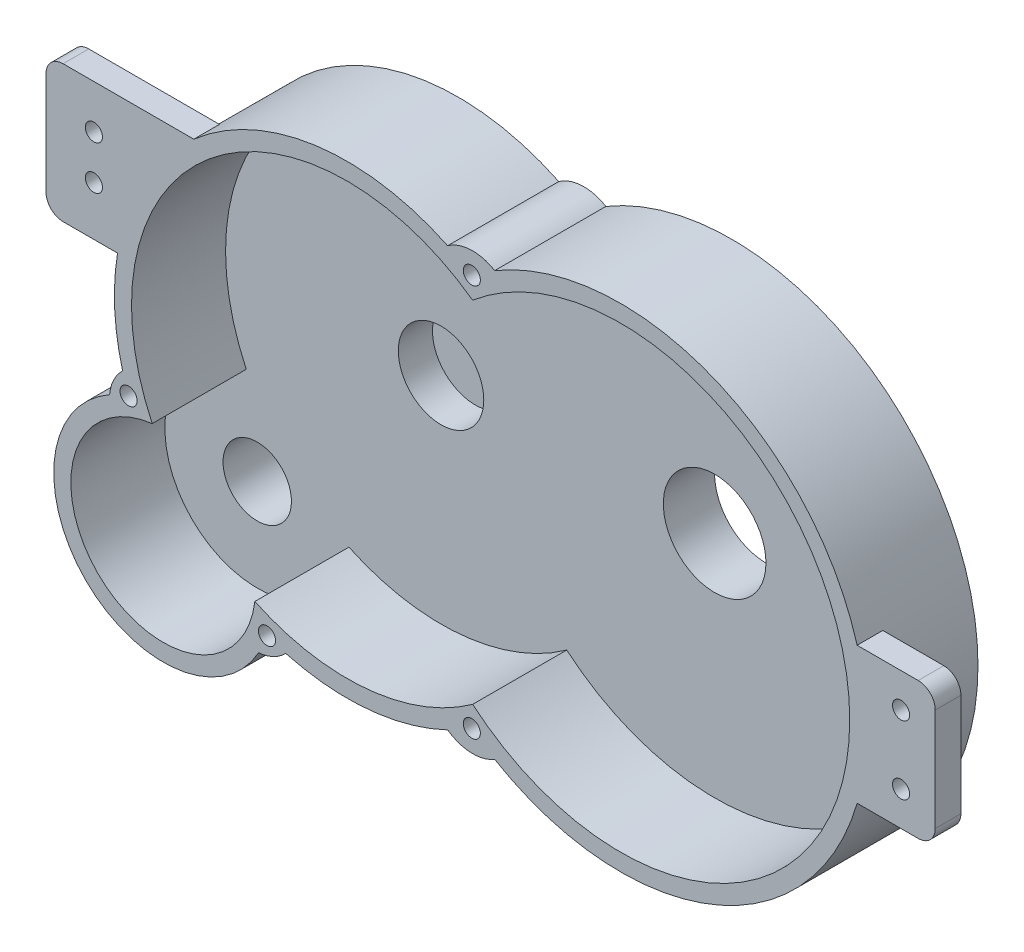
SolidWorks part; units mm, degrees
material "7075-T6 (SN)"
ref_plane "Front Plane" through (0, 0, 0) normal (0, 0, 1) x (1, 0, 0)
ref_plane "Top Plane" through (0, 0, 0) normal (0, 1, 0) x (1, 0, 0)
ref_plane "Right Plane" through (0, 0, 0) normal (1, 0, 0) x (0, 0, -1)
sketch "Sketch1" plane through (0, 0, 0) normal (0, 0, 1) x (1, 0, 0)
  line L1 (92, 0) -> (92, 15)
  line L2 (92, 0) -> (92, -15)
  line L3 (87, 20) -> (69.1665, 20)
  line L4 (87, -20) -> (69.1665, -20)
  line L5 (-168, 16.1707) -> (-168, 46.1707)
  line L6 (-163, 51.1707) -> (-124.7835, 51.1707)
  line L7 (-168, 51.1707) -> (-168, 11.1707)
  line L8 (-163, 11.1707) -> (-147.0762, 11.1707)
  line L9 (-143.8918, 51.1707) -> (-168, 51.1707)
  arc A0 (-43.25, -51.1707) -> (-43.25, 51.1707) centre (0, 0) ccw
  arc A1 (-43.25, 51.1707) -> (-136.9532, -26.932) centre (-80, 0) ccw
  arc A2 (-136.9532, -26.932) -> (-106.932, -56.9532) centre (-133.7401, -53.7401) ccw
  arc A6 (-106.932, -56.9532) -> (-43.25, -51.1707) centre (-80, 0) ccw
  arc A7 (-36.8059, -61.8816) -> (-36.8059, 61.8816) centre (0, 0) ccw
  arc A8 (-145.6003, -17.9054) -> (-149.4051, -25.8366) centre (-136.9532, -26.932) ccw
  circle A9 centre (-143.8541, -23.3805) radius 2.5
  arc A10 (-36.8059, 61.8816) -> (-50.5714, 61.3022) centre (-43.25, 51.1707) ccw
  circle A11 centre (-43.5, 57.3738) radius 2.5
  arc A12 (-105.8366, -69.4051) -> (-97.9054, -65.6003) centre (-106.932, -56.9532) ccw
  arc A13 (-50.5714, -61.3022) -> (-36.8059, -61.8816) centre (-43.25, -51.1707) ccw
  circle A14 centre (-103.3805, -63.8541) radius 2.5
  circle A15 centre (-43.5, -57.3738) radius 2.5
  arc A16 (-149.4051, -25.8366) -> (-105.8366, -69.4051) centre (-133.7401, -53.7401) ccw
  arc A17 (-50.5714, 61.3022) -> (-145.6003, -17.9054) centre (-80, 0) ccw
  arc A18 (-97.9054, -65.6003) -> (-50.5714, -61.3022) centre (-80, 0) ccw
  circle A19 centre (82, 10) radius 2.5
  circle A20 centre (82, -10) radius 2.5
  arc A21 (92, -15) -> (87, -20) centre (87, -15) cw
  arc A22 (92, 15) -> (87, 20) centre (87, 15) ccw
  circle A23 centre (0, 0) radius 15
  circle A24 centre (-80, 0) radius 12.5
  circle A25 centre (-133.7401, -53.7401) radius 10
  circle A26 centre (0, 0) radius 20
  circle A27 centre (-80, 0) radius 17.5
  circle A28 centre (-133.7401, -53.7401) radius 15
  circle A29 centre (-154, 38.378) radius 2.5
  circle A30 centre (-154, 25.5853) radius 2.5
  arc A31 (-168, 46.1707) -> (-163, 51.1707) centre (-163, 46.1707) cw
  arc A32 (-168, 16.1707) -> (-163, 11.1707) centre (-163, 16.1707) ccw
  point P39 (92, -20)
  point P42 (92, 20)
  dimension "D1" = 134
  dimension "D3" = 126
  dimension "D5" = 54
  dimension "D6" = 20
  dimension "D7" = 20
  dimension "D8" = 5
  dimension "D9" = 5
  dimension "D10" = 25
  dimension "D11" = 25
  dimension "D12" = 5
  dimension "D13" = 25
  dimension "D14" = 5
  dimension "D15" = 25
  dimension "D16" = 5
  dimension "D17" = 5
  dimension "D18" = 5
  dimension "D19" = 30
  dimension "D20" = 25
  dimension "D21" = 20
  dimension "D22" = 40
  dimension "D23" = 35
  dimension "D24" = 30
  dimension "D28" = 5
  dimension "D29" = 5
  dimension "D25" = 5
  dimension "D2" = 80
  dimension "D4" = 76
  dimension "D26" = 40
extrude "Boss-Extrude2" add sketch "Sketch1" along normal blind 5 contours A2 A6 A0 A1 A28 A27 A26 | A12 A18 A13 A7 A10 A17 A8 A16 A6 A2 A1 A0 A9 A11 A14 A15 | A25 | A28 A25 | A27 A24 | A26 A23 region at (69.1469, 0, 0) region at (-42.4728, -3.1282, 0) region at (-133.7401, -53.7401, 0) region at (-19.4343, 0, 0) region at (-97.005, 0, 0) region at (-148.3159, -53.7401, 0)
extrude "Boss-Extrude3" add sketch "Sketch1<5>" along normal blind 32.5 contours A12 A18 A13 A7 A10 A17 A8 A16 A6 A2 A1 A0 A9 A11 A14 A15 | L1 A22 L3 A7 L4 A21 L2 A19 A20 region at (81.3627, 0, 0) region at (69.1469, 0, 0)
sketch "Sketch1<5>" plane through (0, 0, 0) normal (0, 0, 1) x (1, 0, 0) same geometry as "Sketch1"
extrude "Cut-Extrude1" cut sketch "Sketch1<6>" along normal blind 25 contours L1 A22 L3 A7 L4 A21 L2 A19 A20 region at (81.3627, 0, 0)
sketch "Sketch1<6>" plane through (0, 0, 0) normal (0, 0, 1) x (1, 0, 0) same geometry as "Sketch1"
extrude "Boss-Extrude4" add sketch "Sketch1<7>" against normal blind 10 contours A27 A24 | A24 | A26 A23 | A23 region at (0, 0, 0) region at (-80, 0, 0) region at (-19.4343, 0, 0) region at (-97.005, 0, 0)
sketch "Sketch1<7>" plane through (0, 0, 0) normal (0, 0, 1) x (1, 0, 0) same geometry as "Sketch1"
extrude "Cut-Extrude2" cut sketch "Sketch1<8>" against normal blind 5 contours A24 | A23 region at (0, 0, 0) region at (-80, 0, 0)
sketch "Sketch1<8>" plane through (0, 0, 0) normal (0, 0, 1) x (1, 0, 0) same geometry as "Sketch1"
extrude "Boss-Extrude5" add sketch "Sketch1<9>" against normal blind 10 contours A28 A25 region at (-148.3159, -53.7401, 0)
sketch "Sketch1<9>" plane through (0, 0, 0) normal (0, 0, 1) x (1, 0, 0) same geometry as "Sketch1"
extrude "Cut-Extrude4" cut sketch "Sketch1<10>" against normal mid plane 10 contours A25 region at (-133.7401, -53.7401, 0)
sketch "Sketch1<10>" plane through (0, 0, 0) normal (0, 0, 1) x (1, 0, 0) same geometry as "Sketch1"
extrude "Cut-Extrude5" cut sketch "Sketch1<11>" against normal blind 10 contours A23 region at (0, 0, 0)
sketch "Sketch1<11>" plane through (0, 0, 0) normal (0, 0, 1) x (1, 0, 0) same geometry as "Sketch1"
extrude "Boss-Extrude7" add sketch "Sketch1<12>" along normal blind 32.5 contours L5 A32 L8 A17 L6 A31 A29 A30 region at (-152.6108, 33.7326, 0)
sketch "Sketch1<12>" plane through (0, 0, 0) normal (0, 0, 1) x (1, 0, 0) same geometry as "Sketch1"
extrude "Cut-Extrude7" cut sketch "Sketch1<14>" along normal blind 25 contours L5 A32 L8 A17 L6 A31 A29 A30 region at (-152.6108, 33.7326, 0)
sketch "Sketch1<14>" plane through (0, 0, 0) normal (0, 0, 1) x (1, 0, 0) same geometry as "Sketch1"
